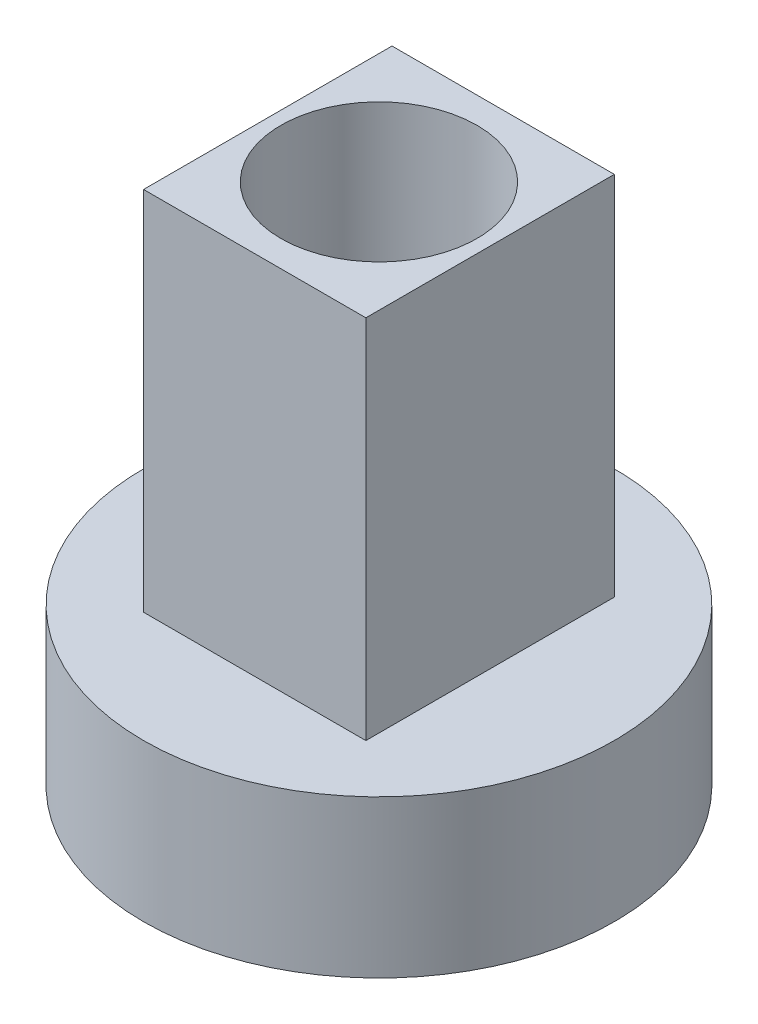
SolidWorks part; units mm, degrees
ref_plane "Спереди" through (0, 0, 0) normal (0, 0, 1) x (1, 0, 0)
ref_plane "Сверху" through (0, 0, 0) normal (0, 1, 0) x (1, 0, 0)
ref_plane "Справа" through (0, 0, 0) normal (1, 0, 0) x (0, 0, -1)
sketch "Эскиз2" plane through (0, 0, 0) normal (0, 1, 0) x (1, 0, 0)
  circle A0 centre (0, 0) radius 90
  dimension "D1" = 180
extrude "Бобышка - Цилиндр" add sketch "Эскиз2" along normal blind 60
sketch "Эскиз4" plane through (0, 60, 0) normal (0, 1, 0) x (1, 0, 0)
  line L1 (-42.5, 47.5) -> (42.5, 47.5)
  line L2 (-42.5, 47.5) -> (-42.5, -47.5)
  line L3 (-42.5, -47.5) -> (42.5, -47.5)
  line L4 (42.5, 47.5) -> (42.5, -47.5)
  line L5 (-42.5, 47.5) -> (42.5, -47.5) construction
  line L6 (-42.5, -47.5) -> (42.5, 47.5) construction
  point P1 (0, 0)
  dimension "A2" = 85
  dimension "A1" = 95
extrude "Бобышка - Паралеллограмм" add sketch "Эскиз4" along normal blind 140
sketch "Эскиз5" plane through (0, 200, 0) normal (0, 1, 0) x (1, 0, 0)
  circle A0 centre (0, 0) radius 37.5
  dimension "D1" = 75
extrude "Вырез центральный" cut sketch "Эскиз5" against normal through all
shell "Оболочка" thickness 3 removed face at (0, 0, 37.5)
